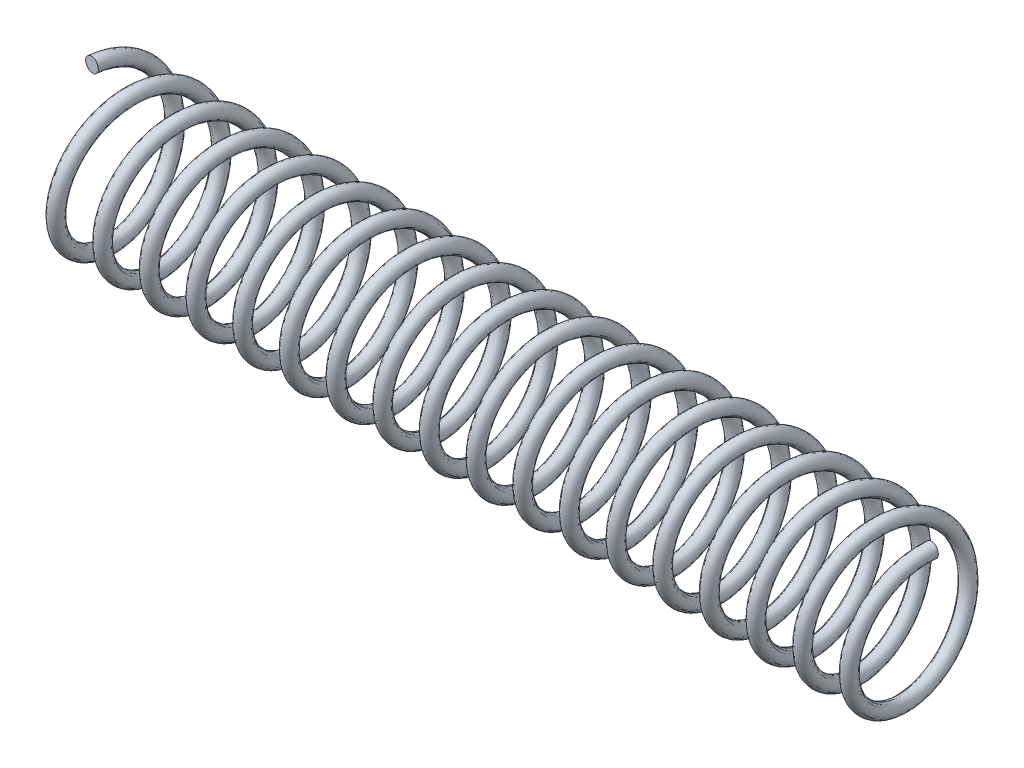
SolidWorks part; units mm, degrees
note: '?' marks a value the reader was unsure of.
ref_plane "Front Plane" through (0, 0, 0) normal (0, 0, 1) x (1, 0, 0)
ref_plane "Top Plane" through (0, 0, 0) normal (0, 1, 0) x (1, 0, 0)
ref_plane "Right Plane" through (0, 0, 0) normal (1, 0, 0) x (0, 0, -1)
sketch "Sketch1" plane through (0, 0, 0) normal (1, 0, 0) x (0, 0, -1)
  circle A0 centre (0, 0) radius 5
  dimension "D1" = 10
curve "Helix/Spiral1" pitch 3.3 height 59.4 turns 18
sweep "Sweep1" add path "Helix/Spiral1" circular profile diameter 1 parameters "D3"=1
ref_axis "Axis1" through (0, 0, 0) along (1, 0, 0)?
